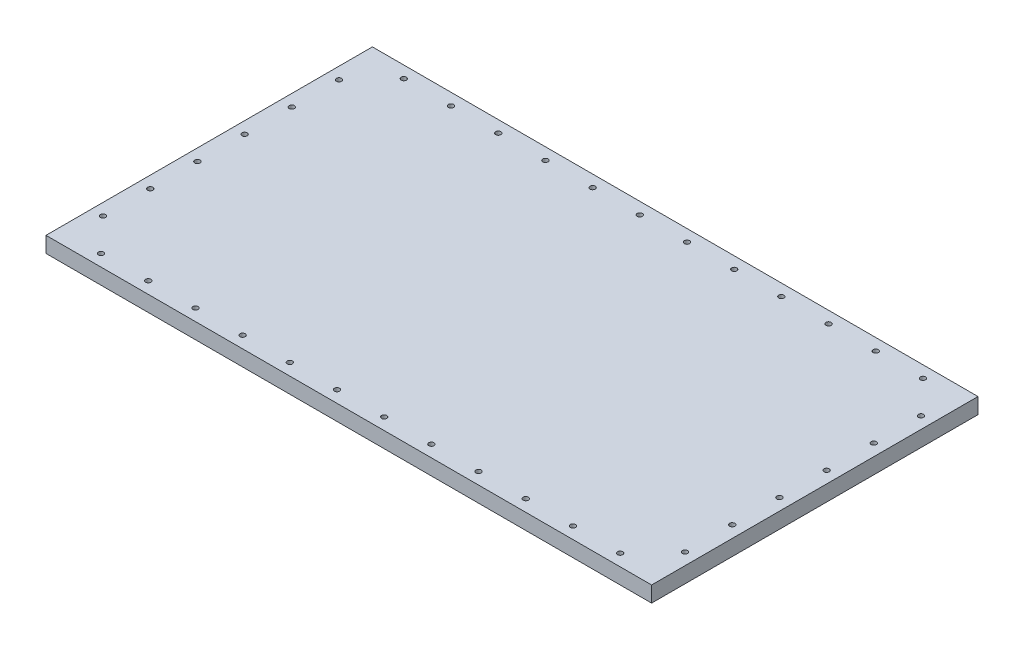
SolidWorks part; units mm, degrees
ref_plane "Front Plane" through (0, 0, 0) normal (0, 0, 1) x (1, 0, 0)
ref_plane "Top Plane" through (0, 0, 0) normal (0, 1, 0) x (1, 0, 0)
ref_plane "Right Plane" through (0, 0, 0) normal (1, 0, 0) x (0, 0, -1)
sketch "Sketch1" plane through (0, 0, 0) normal (0, 0, 1) x (1, 0, 0)
  line L1 (495.3, -12.7) -> (-495.3, -12.7)
  line L2 (495.3, -12.7) -> (495.3, 12.7)
  line L3 (495.3, 12.7) -> (-495.3, 12.7)
  line L4 (-495.3, -12.7) -> (-495.3, 12.7)
  line L5 (495.3, -12.7) -> (-495.3, 12.7) construction
  line L6 (495.3, 12.7) -> (-495.3, -12.7) construction
  line L7 (-495.3, -12.7) -> (-488.95, -12.7)
  line L8 (-495.3, -12.7) -> (-495.3, 12.7)
  line L9 (-495.3, 12.7) -> (-488.95, 12.7)
  line L10 (-488.95, -12.7) -> (-488.95, 12.7)
  line L12 (495.3, -12.7) -> (488.95, -12.7)
  line L13 (495.3, -12.7) -> (495.3, 12.7)
  line L14 (495.3, 12.7) -> (488.95, 12.7)
  line L15 (488.95, -12.7) -> (488.95, 12.7)
  point P0 (0, 0)
  dimension "D1" = 25.4
  dimension "D2" = 990.6
  dimension "D3" = 25.4
  dimension "D4" = 6.35
  dimension "D5" = 6.35
  dimension "D6" = 25.4
extrude "Boss-Extrude1" add sketch "Sketch1" along normal blind 527.05 contours L1 L15 L14 L2 L3 L4 L9 L10 region at (0, 0, 0)
hole_wizard "CSK for 5/16 Flat Head Machine Screw3" positions "Sketch14" profile "Sketch15" countersink size "5/16" standard "ANSI Inch" end condition through all
sketch "Sketch14" plane through (0, -12.7, 0) normal (0, -1, 0) x (-1, 0, 0)
  line L0 (-488.95, -527.05) -> (488.95, -527.05) construction
  line L3 (-488.95, 0) -> (488.95, 0) construction
  line L4 (-488.95, -527.05) -> (-488.95, 0) construction
  line L7 (488.95, -527.05) -> (488.95, 0) construction
  point P0 (419.1, -508)
  point P10 (342.9, -508)
  point P11 (266.7, -508)
  point P12 (190.5, -508)
  point P13 (114.3, -508)
  point P14 (38.1, -508)
  point P15 (-38.1, -508)
  point P16 (-114.3, -508)
  point P17 (-190.5, -508)
  point P18 (-266.7, -508)
  point P35 (419.1, -19.05)
  point P36 (342.9, -19.05)
  point P37 (266.7, -19.05)
  point P38 (190.5, -19.05)
  point P39 (114.3, -19.05)
  point P40 (38.1, -19.05)
  point P41 (-38.1, -19.05)
  point P42 (-114.3, -19.05)
  point P43 (-190.5, -19.05)
  point P44 (-266.7, -19.05)
  point P51 (-342.9, -508)
  point P52 (-342.9, -19.05)
  point P53 (-419.1, -508)
  point P54 (-419.1, -19.05)
  dimension "D1" = 19.05
  dimension "D2" = 76.2
  dimension "D4" = 3
  dimension "D6" = 19.05
  dimension "D7" = 69.85
  dimension "D8" = 69.85
  dimension "D3" = 10
  dimension "D5" = 2
sketch "Sketch15" plane through (-419.1, -12.7, 508) normal (1, 0, 0) x (0, 0, -1)
  line L0 (0, 0) -> (0, 25.4)
  line L1 (0, 25.4) -> (4.2164, 25.4)
  line L2 (4.2164, 25.4) -> (4.2164, 4.4267)
  line L3 (4.2164, 4.4267) -> (8.0645, 0)
  line L5 (8.0645, 0) -> (0, 0)
  line L6 (-4.2164, 4.4267) -> (-8.0645, 0) construction
  line L11 (0, -6.35) -> (0, 107.95) construction
  dimension "Thru Hole Dia." = 8.4328
  dimension "Thru Hole Depth" = 25.4
  dimension "Near C'Sink Dia." = 16.129
  dimension "Near C'Sink Angle" = 82
hole_wizard "CSK for 5/16 Flat Head Machine Screw4" positions "Sketch16" profile "Sketch17" countersink size "5/16" standard "ANSI Inch" end condition through all
sketch "Sketch16" plane through (0, -12.7, 0) normal (0, -1, 0) x (-1, 0, 0)
  line L0 (-488.95, -527.05) -> (488.95, -527.05) construction
  line L1 (-488.95, 0) -> (488.95, 0) construction
  line L5 (488.95, -527.05) -> (488.95, 0) construction
  line L6 (-488.95, -527.05) -> (-488.95, 0) construction
  point P0 (469.9, -454.025)
  point P10 (469.9, -377.825)
  point P11 (469.9, -301.625)
  point P12 (469.9, -225.425)
  point P13 (469.9, -149.225)
  point P14 (469.9, -73.025)
  point P33 (-469.9, -454.025)
  point P34 (-469.9, -377.825)
  point P35 (-469.9, -301.625)
  point P36 (-469.9, -225.425)
  point P37 (-469.9, -149.225)
  point P38 (-469.9, -73.025)
  dimension "D1" = 73.025
  dimension "D3" = 73.025
  dimension "D4" = 19.05
  dimension "D6" = 19.05
  dimension "D2" = 6
  dimension "D5" = 2
sketch "Sketch17" plane through (-469.9, -12.7, 454.025) normal (1, 0, 0) x (0, 0, -1)
  line L0 (0, 0) -> (0, 25.4)
  line L1 (0, 25.4) -> (4.2164, 25.4)
  line L2 (4.2164, 25.4) -> (4.2164, 4.4267)
  line L3 (4.2164, 4.4267) -> (8.0645, 0)
  line L5 (8.0645, 0) -> (0, 0)
  line L6 (-4.2164, 4.4267) -> (-8.0645, 0) construction
  line L11 (0, -6.35) -> (0, 107.95) construction
  dimension "Thru Hole Dia." = 8.4328
  dimension "Thru Hole Depth" = 25.4
  dimension "Near C'Sink Dia." = 16.129
  dimension "Near C'Sink Angle" = 82
